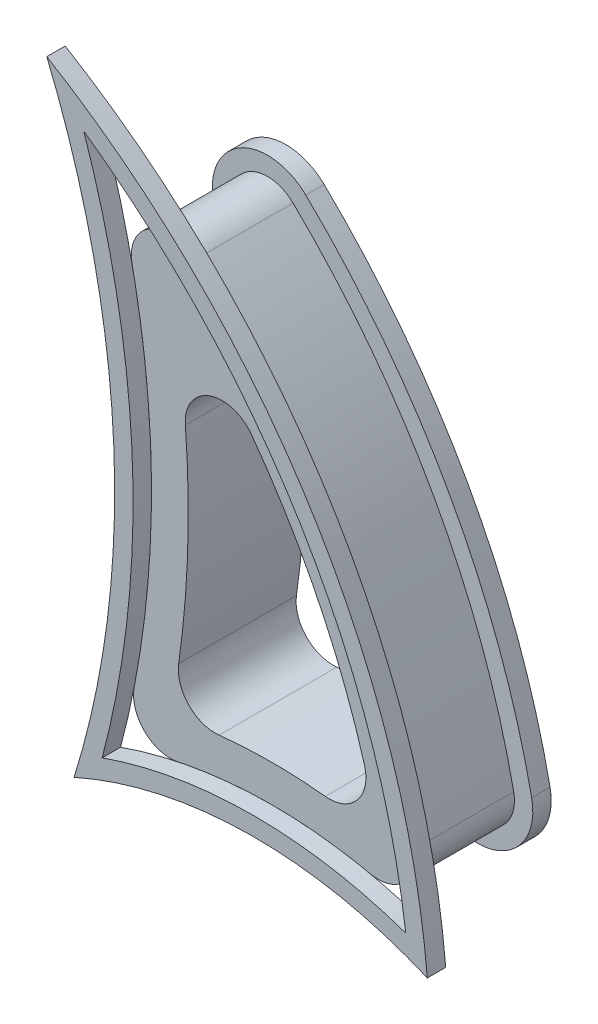
SolidWorks part; units mm, degrees
note: The reader was unsure of these and kept them because the rebuilt part matched: shared geometry of "Sketch1<3>", "Sketch1<4>".
ref_plane "Front Plane" through (0, 0, 0) normal (0, 0, 1) x (1, 0, 0)
ref_plane "Top Plane" through (0, 0, 0) normal (0, 1, 0) x (1, 0, 0)
ref_plane "Right Plane" through (0, 0, 0) normal (1, 0, 0) x (0, 0, -1)
sketch "Sketch1" plane through (0, 0, 0) normal (0, 0, 1) x (1, 0, 0)
  line L0 (-62.581, 0) -> (66.6392, 0) construction
  line L1 (0, 51.2609) -> (0, -45.2805) construction
  arc A0 (-8.25, 0) -> (8.25, 0) centre (0, -23.5995) cw
  arc A1 (8.25, 0) -> (-9.25, 29) centre (-33.4069, -5.3576) ccw
  arc A2 (-8.25, 0) -> (-9.25, 29) centre (-56.5703, 12.851) ccw
  arc A3 (9.4221, -1.5264) -> (-11.2574, 31.4989) centre (-33.4069, -5.3576) ccw
  arc A4 (-9.7745, -1.6802) -> (-11.2574, 31.4989) centre (-56.5703, 12.851) ccw
  arc A5 (-9.7745, -1.6802) -> (9.4221, -1.5264) centre (0, -23.5995) cw
  arc A6 (5.7567, 2.7796) -> (-5.6635, 23.4574) centre (-33.4069, -5.3576) ccw
  arc A7 (-5.5461, 2.8247) -> (-5.6635, 23.4574) centre (-56.5703, 12.851) ccw
  arc A8 (-5.5461, 2.8247) -> (5.7567, 2.7796) centre (0, -23.5995) cw
  dimension "D1" = 25
  dimension "D5" = 42
  dimension "D6" = 50
  dimension "D2" = 17.5
  dimension "D3" = 16.5
  dimension "D4" = 29
  dimension "D7" = 1
  dimension "D8" = 2
extrude "Boss-Extrude1" add sketch "Sketch1" along normal blind 6.4 contours A2 A0 A1 A8 A7 A6
extrude "Boss-Extrude2" add sketch "Sketch1<3>" along normal blind 1 contours A4 A5 A3 A0 A2 A1
sketch "Sketch1<3>" plane through (0, 0, 0) normal (0, 0, 1) x (1, 0, 0) same geometry as "Sketch1"
extrude "Boss-Extrude3" add sketch "Sketch1<4>" along normal blind 1 from surface at 6.4 contours A4 A5 A3 A0 A2 A1 starting at face at (-0.9519, 10.176, 6.4)
sketch "Sketch1<4>" plane through (0, 0, 0) normal (0, 0, 1) x (1, 0, 0) same geometry as "Sketch1"
fillet "Fillet1" radius 2 3 edges at (8.25, 0, 3.7) (-8.25, 0, 3.7) (-9.25, 29, 3.7)
fillet "Fillet2" radius 2 3 edges at (-5.5461, 2.8247, 3.2) (5.7567, 2.7796, 3.2) (-5.6635, 23.4574, 3.2)
fillet "Fillet3" radius 3 3 edges at (-11.2574, 31.4989, 0.5) (9.4221, -1.5264, 0.5) (-9.7745, -1.6802, 0.5)
